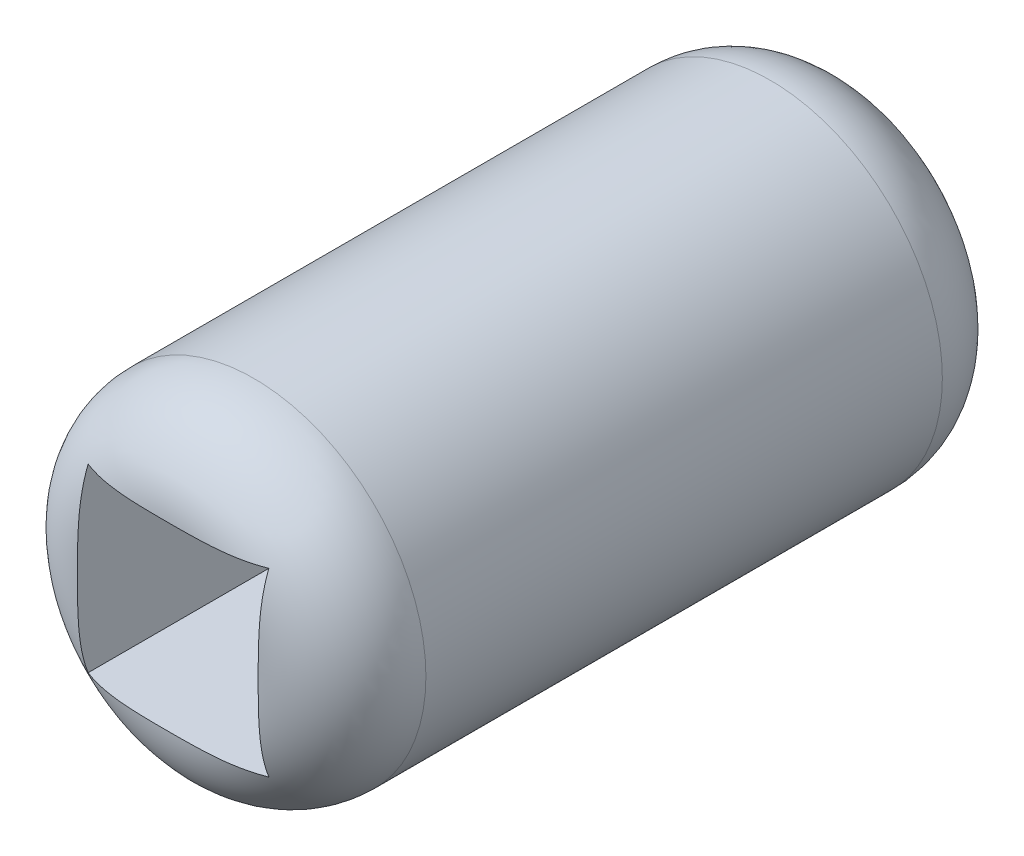
SolidWorks part; units mm, degrees
ref_plane "Front" through (0, 0, 0) normal (0, 0, 1) x (1, 0, 0)
ref_plane "Top" through (0, 0, 0) normal (0, 1, 0) x (1, 0, 0)
ref_plane "Right" through (0, 0, 0) normal (1, 0, 0) x (0, 0, -1)
sketch "Support-Front" plane through (0, 0, 0) normal (0, 0, 1) x (1, 0, 0)
  line L0 (10, 0) -> (-10, 0) construction
  line L1 (-10, -10) -> (10, -10)
  line L2 (-10, -10) -> (-10, 10)
  line L3 (-10, 10) -> (10, 10)
  line L4 (10, -10) -> (10, 10)
  line L5 (0, 10) -> (0, -10) construction
  dimension "Height-Profile" = 20
  dimension "Width-Profile" = 20
sketch "Support-Right-Length" plane through (0, 0, 0) normal (1, 0, 0) x (0, 0, -1)
  line L0 (0, -10) -> (0, 10) construction
  line L1 (-25, 10) -> (25, 10)
  line L2 (-25, 10) -> (-25, -10)
  line L3 (-25, -10) -> (25, -10)
  line L4 (25, 10) -> (25, -10)
  dimension "Length-Profile" = 50
sketch "Support-Profile" plane through (0, 0, 0) normal (0, 0, 1) x (1, 0, 0)
  line L8 (4.9176, -8.2) -> (2.8, -8.2)
  line L9 (2.5, -8.5) -> (2.5, -9.2)
  line L10 (3.3, -10) -> (8, -10)
  line L11 (10, -8) -> (10, -3.3)
  line L24 (9.2, -2.5) -> (8.5, -2.5)
  line L25 (8.2, -2.8) -> (8.2, -4.9176)
  line L26 (6.779, -5.5062) -> (4.5287, -3.2559)
  line L27 (3.65, -1.1346) -> (3.65, 1.1346)
  line L28 (4.5287, 3.2559) -> (6.779, 5.5062)
  line L29 (8.2, 4.9176) -> (8.2, 2.8)
  line L30 (8.5, 2.5) -> (9.2, 2.5)
  line L31 (10, 3.3) -> (10, 8)
  line L32 (8, 10) -> (3.3, 10)
  line L33 (2.5, 9.2) -> (2.5, 8.5)
  line L34 (2.8, 8.2) -> (4.9176, 8.2)
  line L35 (5.5062, 6.779) -> (3.2559, 4.5287)
  line L40 (1.1346, 3.65) -> (-1.1346, 3.65)
  line L41 (-3.2559, 4.5287) -> (-5.5062, 6.779)
  line L42 (-4.9176, 8.2) -> (-2.8, 8.2)
  line L43 (-2.5, 8.5) -> (-2.5, 9.2)
  line L44 (-3.3, 10) -> (-8, 10)
  line L45 (-10, 8) -> (-10, 3.3)
  line L46 (-9.2, 2.5) -> (-8.5, 2.5)
  line L47 (-8.2, 2.8) -> (-8.2, 4.9176)
  line L48 (-6.779, 5.5062) -> (-4.5287, 3.2559)
  line L49 (-3.65, 1.1346) -> (-3.65, -1.1346)
  line L50 (-4.5287, -3.2559) -> (-6.779, -5.5062)
  line L51 (-8.2, -4.9176) -> (-8.2, -2.8)
  line L52 (-8.5, -2.5) -> (-9.2, -2.5)
  line L53 (-10, -3.3) -> (-10, -8)
  line L54 (-8, -10) -> (-3.3, -10)
  line L55 (-2.5, -9.2) -> (-2.5, -8.5)
  line L56 (-2.8, -8.2) -> (-4.9176, -8.2)
  line L57 (-5.5062, -6.779) -> (-3.2559, -4.5287)
  line L58 (-1.1346, -3.65) -> (1.1346, -3.65)
  line L59 (3.2559, -4.5287) -> (5.5062, -6.779)
  circle A2 centre (0, 0) radius 2.15
  arc A3 (2.8, -8.2) -> (2.5, -8.5) centre (2.8, -8.5) ccw
  arc A5 (2.5, -9.2) -> (3.3, -10) centre (3.3, -9.2) ccw
  arc A24 (8, -10) -> (10, -8) centre (8, -8) ccw
  arc A25 (10, -3.3) -> (9.2, -2.5) centre (9.2, -3.3) ccw
  arc A26 (8.5, -2.5) -> (8.2, -2.8) centre (8.5, -2.8) ccw
  arc A27 (6.779, -5.5062) -> (8.2, -4.9176) centre (7.3676, -4.9176) ccw
  arc A28 (3.65, -1.1346) -> (4.5287, -3.2559) centre (6.65, -1.1346) ccw
  arc A29 (4.5287, 3.2559) -> (3.65, 1.1346) centre (6.65, 1.1346) ccw
  arc A30 (8.2, 4.9176) -> (6.779, 5.5062) centre (7.3676, 4.9176) ccw
  arc A31 (8.2, 2.8) -> (8.5, 2.5) centre (8.5, 2.8) ccw
  arc A32 (9.2, 2.5) -> (10, 3.3) centre (9.2, 3.3) ccw
  arc A33 (10, 8) -> (8, 10) centre (8, 8) ccw
  arc A34 (3.3, 10) -> (2.5, 9.2) centre (3.3, 9.2) ccw
  arc A35 (2.5, 8.5) -> (2.8, 8.2) centre (2.8, 8.5) ccw
  arc A38 (5.5062, 6.779) -> (4.9176, 8.2) centre (4.9176, 7.3676) ccw
  arc A39 (1.1346, 3.65) -> (3.2559, 4.5287) centre (1.1346, 6.65) ccw
  arc A44 (-3.2559, 4.5287) -> (-1.1346, 3.65) centre (-1.1346, 6.65) ccw
  arc A45 (-4.9176, 8.2) -> (-5.5062, 6.779) centre (-4.9176, 7.3676) ccw
  arc A46 (-2.8, 8.2) -> (-2.5, 8.5) centre (-2.8, 8.5) ccw
  arc A47 (-2.5, 9.2) -> (-3.3, 10) centre (-3.3, 9.2) ccw
  arc A48 (-8, 10) -> (-10, 8) centre (-8, 8) ccw
  arc A49 (-10, 3.3) -> (-9.2, 2.5) centre (-9.2, 3.3) ccw
  arc A50 (-8.5, 2.5) -> (-8.2, 2.8) centre (-8.5, 2.8) ccw
  arc A51 (-6.779, 5.5062) -> (-8.2, 4.9176) centre (-7.3676, 4.9176) ccw
  arc A52 (-3.65, 1.1346) -> (-4.5287, 3.2559) centre (-6.65, 1.1346) ccw
  arc A53 (-4.5287, -3.2559) -> (-3.65, -1.1346) centre (-6.65, -1.1346) ccw
  arc A54 (-8.2, -4.9176) -> (-6.779, -5.5062) centre (-7.3676, -4.9176) ccw
  arc A55 (-8.2, -2.8) -> (-8.5, -2.5) centre (-8.5, -2.8) ccw
  arc A56 (-9.2, -2.5) -> (-10, -3.3) centre (-9.2, -3.3) ccw
  arc A57 (-10, -8) -> (-8, -10) centre (-8, -8) ccw
  arc A58 (-3.3, -10) -> (-2.5, -9.2) centre (-3.3, -9.2) ccw
  arc A59 (-2.5, -8.5) -> (-2.8, -8.2) centre (-2.8, -8.5) ccw
  arc A60 (-5.5062, -6.779) -> (-4.9176, -8.2) centre (-4.9176, -7.3676) ccw
  arc A61 (-1.1346, -3.65) -> (-3.2559, -4.5287) centre (-1.1346, -6.65) ccw
  arc A62 (3.2559, -4.5287) -> (1.1346, -3.65) centre (1.1346, -6.65) ccw
  arc A63 (4.9176, -8.2) -> (5.5062, -6.779) centre (4.9176, -7.3676) ccw
ref_plane "Ref-Plane-1" through (0, 0, 25) normal (0, 0, 1) x (1, 0, 0)
ref_plane "Ref-Plane-2" through (0, 0, -25) normal (0, 0, 1) x (1, 0, 0)
sketch "Sketch4" plane through (0, 0, 25) normal (0, 0, 1) x (1, 0, 0)
  circle A0 centre (0, 0) radius 20
  dimension "D1" = 40
extrude "Body" add sketch "Sketch4" against normal blind 80
sketch "Sketch16" plane through (0, 0, 0) normal (0, 0, 1) x (1, 0, 0)
  line L1 (-10.5, -10.5) -> (10.5, -10.5)
  line L2 (-10.5, -10.5) -> (-10.5, 10.5)
  line L3 (-10.5, 10.5) -> (10.5, 10.5)
  line L4 (10.5, -10.5) -> (10.5, 10.5)
  line L5 (-10.5, -10.5) -> (10.5, 10.5) construction
  line L6 (-10.5, 10.5) -> (10.5, -10.5) construction
  point P0 (0, 0)
  dimension "D1" = 21
  dimension "D2" = 21
extrude "Cut-Extrude1" cut sketch "Sketch16" against normal blind 50 and the other way blind 50
sketch "Sketch17" plane through (0, 0, -55) normal (0, 0, -1) x (-1, 0, 0)
  circle A0 centre (0, 0) radius 2.55
  dimension "D1" = 5.1
extrude "Cut-Extrude2" cut sketch "Sketch17" against normal blind 55 contours A0
sketch "Sketch18" plane through (0, 0, -55) normal (0, 0, -1) x (-1, 0, 0)
  circle A0 centre (0, 0) radius 7
  dimension "D1" = 14
extrude "Cut-Extrude3" cut sketch "Sketch18" against normal blind 3
fillet "Fillet1" radius 10 2 edges at (20, 0, 25) (20, 0, -55)
